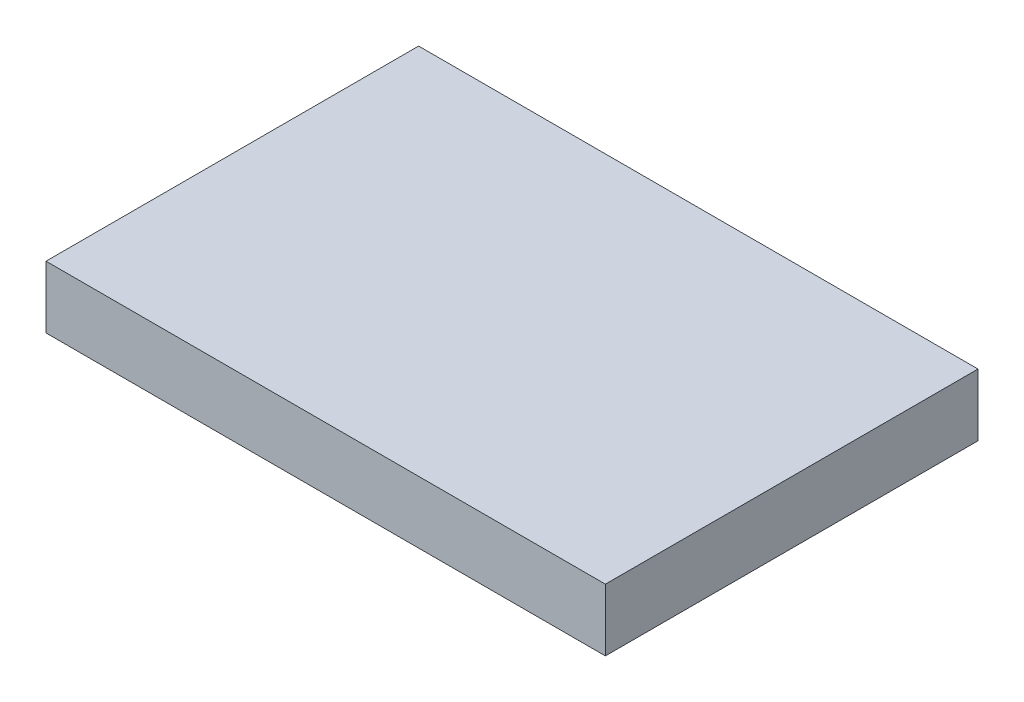
SolidWorks part; units mm, degrees
ref_plane "Front Plane" through (0, 0, 0) normal (0, 0, 1) x (1, 0, 0)
ref_plane "Top Plane" through (0, 0, 0) normal (0, 1, 0) x (1, 0, 0)
ref_plane "Right Plane" through (0, 0, 0) normal (1, 0, 0) x (0, 0, -1)
sketch "Sketch1" plane through (0, 0, 0) normal (0, 1, 0) x (1, 0, 0)
  line L1 (0, 0) -> (-114.261, 0)
  line L2 (0, 0) -> (0, 76.1093)
  line L3 (0, 76.1093) -> (-114.261, 76.1093)
  line L4 (-114.261, 0) -> (-114.261, 76.1093)
extrude "Boss-Extrude1" add sketch "Sketch1" against normal blind 12.7 contours L2 L1 L4 L3
sketch "Sketch2" plane through (0, -12.7, 0) normal (0, -1, 0) x (1, 0, 0)
  line L0 (0, -38.0546) -> (-114.261, -38.0546)
  line L1 (0, 0) -> (0, -76.1093) construction
  line L2 (-114.261, 0) -> (-114.261, -76.1093) construction
  line L3 (-57.1305, 0) -> (-57.1305, -76.1093)
  line L4 (0, 0) -> (-114.261, 0) construction
  line L5 (0, -76.1093) -> (-114.261, -76.1093) construction
  circle A0 centre (-10.0357, -14.0297) radius 6.4654
  circle A1 centre (-10.0357, -62.0796) radius 6.3185
  circle A2 centre (-104.2254, -14.0297) radius 6.3185
  circle A3 centre (-104.2254, -62.0796) radius 6.4654
